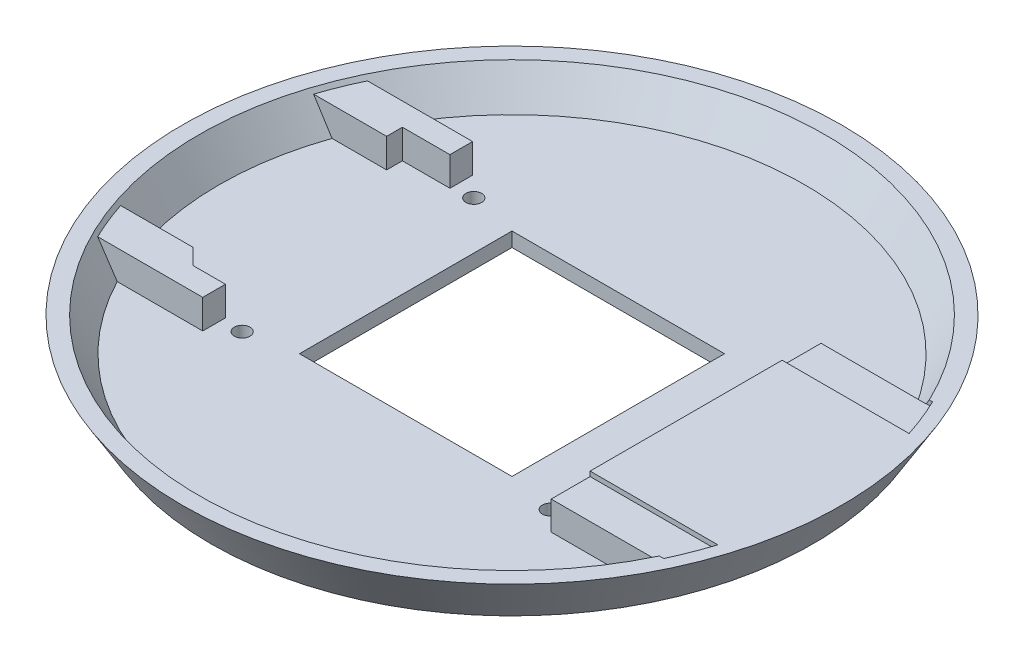
SolidWorks part; units mm, degrees
ref_plane "Front Plane" through (0, 0, 0) normal (0, 0, 1) x (1, 0, 0)
ref_plane "Top Plane" through (0, 0, 0) normal (0, 1, 0) x (1, 0, 0)
ref_plane "Right Plane" through (0, 0, 0) normal (1, 0, 0) x (0, 0, -1)
sketch "Sketch1" plane through (0, 0, 0) normal (0, 0, 1) x (1, 0, 0)
  line L0 (0, 0) -> (63, 0)
  line L1 (63, 0) -> (69, 10)
  line L6 (0, 3) -> (61.3014, 3)
  line L7 (61.3014, 3) -> (65.5014, 10)
  line L8 (69, 10) -> (65.5014, 10)
  line L9 (0, 0) -> (0, 3)
  line L10 (61.3014, 3) -> (66.4275, 11.5435) construction
  dimension "D1" = 69
  dimension "D2" = 63
  dimension "D3" = 10
  dimension "D4" = 3
revolve "Revolve1" add sketch "Sketch1" angle 360 about L9
sketch "Sketch2" plane through (0, 3, 0) normal (0, 1, 0) x (1, 0, 0)
  line L1 (-22.25, 22.25) -> (22.25, 22.25)
  line L2 (-22.25, 22.25) -> (-22.25, -22.25)
  line L3 (-22.25, -22.25) -> (22.25, -22.25)
  line L4 (22.25, 22.25) -> (22.25, -22.25)
  line L5 (-22.25, 22.25) -> (22.25, -22.25) construction
  line L6 (-22.25, -22.25) -> (22.25, 22.25) construction
  circle A0 centre (-32.25, 24.25) radius 1.65
  circle A1 centre (32.25, 24.25) radius 1.65
  circle A2 centre (-32.25, -24.25) radius 1.65
  circle A3 centre (32.25, -24.25) radius 1.65
  point P0 (0, 0)
  dimension "D3" = 3.3
  dimension "D5" = 10
  dimension "D6" = 10
  dimension "D7" = 10
  dimension "D9" = 2
  dimension "D10" = 2
  dimension "D11" = 2
  dimension "D1" = 44.5
  dimension "D2" = 44.5
  dimension "D4" = 10
  dimension "D8" = 2
  dimension "D12" = 0
  dimension "D13" = 0
extrude "Cut-Extrude1" cut sketch "Sketch2" against normal through all
sketch "Sketch4" plane through (0, 0, 0) normal (1, 0, 0) x (0, 0, -1)
  line L0 (69, 10) -> (-69, 10) construction
  line L1 (-28.25, 10) -> (28.25, 10)
  line L2 (-28.25, 10) -> (-28.25, 3)
  line L3 (-28.25, 3) -> (28.25, 3)
  line L4 (28.25, 10) -> (28.25, 3)
  line L5 (61.3014, 3) -> (-61.3014, 3) construction
  line L6 (28.25, 9.3) -> (28.25, 3) construction
  line L7 (-28.25, 3) -> (-28.25, 9.3) construction
  dimension "D1" = 0
  dimension "D2" = 0
  dimension "D3" = 0
extrude "Boss-Extrude1" add sketch "Sketch4" along normal up to next from offset 36.45
sketch "Sketch5" plane through (0, 10, 0) normal (0, 1, 0) x (1, 0, 0)
  line L0 (60.0162, -28.25) -> (36.45, -28.25)
  line L1 (36.45, -28.25) -> (36.45, -20.1)
  line L2 (36.45, -20.1) -> (63.1942, -20.1)
  line L3 (63.0344, 20.1) -> (36.45, 20.1)
  line L4 (36.45, 20.1) -> (36.45, 28.3)
  line L5 (36.45, 28.3) -> (59.7554, 28.3)
  line L6 (59.0963, -28.25) -> (36.45, -28.25) construction
  line L7 (59.514, 28.3) -> (-46.25, 28.3) construction
  line L8 (62.6955, 20.3) -> (-28.25, 20.3) construction
  line L9 (62.6955, -20.3) -> (-28.25, -20.3) construction
  line L10 (36.45, 28.25) -> (36.45, -28.25) construction
  arc A0 (63.0344, 20.1) -> (59.7554, 28.3) centre (0.25, -0.25) ccw
  arc A1 (60.0162, -28.25) -> (63.1942, -20.1) centre (0.25, -0.25) ccw
  dimension "D1" = 132
  dimension "D2" = 0
  dimension "D3" = 0
  dimension "D4" = 0.2
  dimension "D5" = 0.2
  dimension "D6" = 0
  dimension "D7" = 0
extrude "Cut-Extrude2" cut sketch "Sketch5" against normal blind 1
sketch "Sketch6" plane through (0, 0, 0) normal (1, 0, 0) x (0, 0, -1)
  line L0 (28.25, 9.3) -> (28.25, 3) construction
  line L1 (28.25, 9.1) -> (23.5, 9.1)
  line L2 (28.25, 9.1) -> (28.25, 3)
  line L3 (28.25, 3) -> (23.5, 3)
  line L4 (23.5, 9.1) -> (23.5, 3)
  line L5 (-28.25, 9.1) -> (-23.5, 9.1)
  line L6 (-28.25, 9.1) -> (-28.25, 3)
  line L7 (-28.25, 3) -> (-23.5, 3)
  line L8 (-23.5, 9.1) -> (-23.5, 3)
  line L9 (-28.25, 3) -> (-28.25, 9.3) construction
  line L10 (-28.25, 9.3) -> (28.25, 9.3) construction
  line L11 (-23.3, 9.3) -> (-23.3, 3) construction
  line L12 (23.3, 9.3) -> (23.3, 3) construction
  dimension "D1" = 3
  dimension "D2" = 3
  dimension "D3" = 0
  dimension "D4" = 0
  dimension "D5" = 0.2
  dimension "D6" = 0.2
  dimension "D7" = 0.2
  dimension "D8" = 0.2
extrude "Boss-Extrude2" add sketch "Sketch6" against normal up to next from offset 36.5 offset against normal yes
sketch "Sketch7" plane through (0, 0, 0) normal (0, 0, 1) x (1, 0, 0)
  line L0 (-58.6182, 3) -> (-46.45, 3)
  line L2 (-46.45, 9.1) -> (-46.45, 3)
  line L6 (-46.25, 3) -> (-46.25, 9.3) construction
  line L11 (-46.45, 9.1) -> (-60.5618, 9.1)
  line L19 (-58.6182, 3) -> (-62.5618, 9.1)
  line L20 (-62.5618, 9.1) -> (-60.5618, 9.1)
  dimension "D1" = 6.1
  dimension "D2" = 2
  dimension "D3" = 0.2
  dimension "D5" = 6.1
  dimension "D7" = 3.9437
extrude "Boss-Extrude3" add sketch "Sketch7" along normal up to surface (23.5 mm away) from offset 20.2 up to face at (-48.038, 6.8125, 23.5)
extrude "Boss-Extrude4" add sketch "Sketch7<2>" against normal up to surface (23.5 mm away) from offset 20.2 up to face at (-47.052, 5.2875, -23.5) offset against normal yes
sketch "Sketch7<2>" plane through (0, 0, 0) normal (0, 0, 1) x (1, 0, 0) same geometry as "Sketch7"
chamfer "Chamfer1" distance 3.2 angle 45 1 edges at (-46.45, 6.05, 23.5)
sketch "Sketch9" plane through (-33.375, 0, 33.375) normal (0.7071, 0, -0.7071) x (-0.7071, 0, -0.7071)
  line L0 (13.9654, 3) -> (13.9654, 9.1) construction
  line L1 (16.9654, 9.1) -> (19.9654, 9.1)
  line L2 (16.9654, 9.1) -> (16.9654, 3)
  line L3 (16.9654, 3) -> (19.9654, 3)
  line L4 (19.9654, 9.1) -> (19.9654, 3)
  line L5 (13.9654, 9.1) -> (18.4908, 9.1) construction
  line L6 (18.4908, 3) -> (13.9654, 3) construction
  dimension "D1" = 3
  dimension "D2" = 3
  dimension "D3" = 0
  dimension "D4" = 0
extrude "Cut-Extrude4" cut sketch "Sketch9" along normal up to vertex (0.0707 mm away) up to point (-46.45, 9.1, 20.2)
